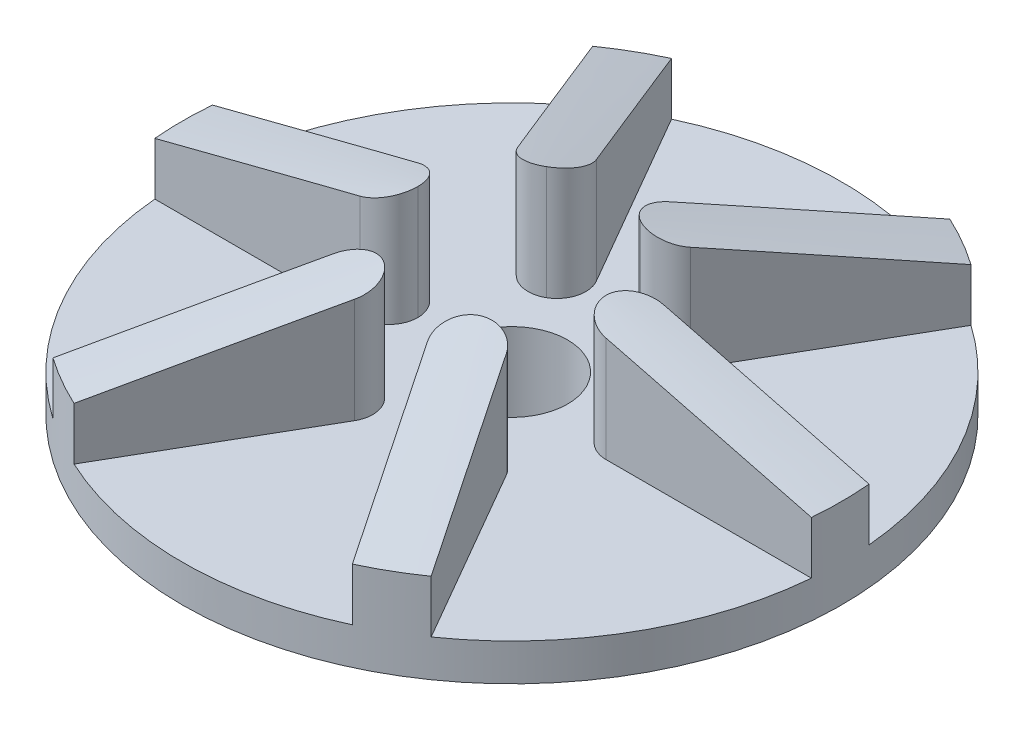
SolidWorks part; units mm, degrees
ref_plane "Front Plane" through (0, 0, 0) normal (0, 0, 1) x (1, 0, 0)
ref_plane "Top Plane" through (0, 0, 0) normal (0, 1, 0) x (1, 0, 0)
ref_plane "Right Plane" through (0, 0, 0) normal (1, 0, 0) x (0, 0, -1)
sketch "Sketch1" plane through (0, 0, 0) normal (0, 1, 0) x (1, 0, 0)
  circle A0 centre (0, 0) radius 17.78
  dimension "D1" = 35.56
extrude "base" add sketch "Sketch1" along normal blind 2
sketch "Sketch2" plane through (0, 0, 0) normal (0, -1, 0) x (1, 0, 0)
  circle A0 centre (0, 0) radius 8
  dimension "D1" = 16
extrude "boss" add sketch "Sketch2" along normal blind 5
sketch "Sketch3" plane through (0, 2, 0) normal (0, 1, 0) x (1, 0, 0)
  line L0 (5.08, 0) -> (17.78, 0) construction
  line L1 (4.8359, 1.5559) -> (17.7118, 1.5559)
  line L2 (4.8359, -1.5559) -> (17.7118, -1.5559)
  circle A0 centre (0, 0) radius 5.08 construction
  circle A1 centre (0, 0) radius 17.78 construction
  arc A2 (4.8359, -1.5559) -> (4.8359, 1.5559) centre (0, 0) ccw
  arc A3 (17.7118, -1.5559) -> (17.7118, 1.5559) centre (0, 0) ccw
  dimension "D1" = 10.16
  dimension "D2" = 1.5559
  dimension "D3" = 1.5559
extrude "blade" add sketch "Sketch3" along normal blind 6.1242
pattern_circular "blade pattern" count 6 over 360 about axis through (0, 0, 0) along (0, 1, 0) of "blade"
sketch "Sketch5" plane through (0, 0, 0) normal (0, 0, 1) x (1, 0, 0)
  line L0 (-17.78, 8.1242) -> (-17.78, 4.8372)
  line L2 (-17.78, 4.8372) -> (-5.08, 8.1242)
  line L3 (-5.08, 8.1242) -> (-17.78, 8.1242)
  line L4 (-10.2034, 2) -> (-17.7118, 2) construction
  line L5 (0, 0) -> (0, 16.9753) construction
  dimension "D1" = 2.8372
  dimension "D2" = 6.1242
  dimension "D3" = 17.78
  dimension "D4" = 5.08
revolve "angle trim" cut sketch "Sketch5" angle 360 about L5
sketch "Sketch6" plane through (0, -5, 0) normal (0, -1, 0) x (-1, 0, 0)
  circle A0 centre (0, 0) radius 3
  dimension "D1" = 6
extrude "bore_cut" cut sketch "Sketch6" against normal blind 20
sketch "Sketch7" plane through (0, -5, 0) normal (0, -1, 0) x (1, 0, 0)
  line L1 (-5, -1) -> (5, -1)
  line L2 (-5, -1) -> (-5, 1) construction
  line L3 (-5, 1) -> (5, 1)
  line L4 (5, -1) -> (5, 1) construction
  line L5 (-5, -1) -> (5, 1) construction
  line L6 (-5, 1) -> (5, -1) construction
  arc A0 (-5, 1) -> (-5, -1) centre (-5, 0) ccw
  arc A1 (5, -1) -> (5, 1) centre (5, 0) ccw
  point P0 (0, 0)
  dimension "D1" = 2
  dimension "D2" = 10
extrude "dowel cut" cut sketch "Sketch7" against normal blind 2
fillet "Fillet1" radius 1.5559 12 edges at (-4.8359, 5.0621, -1.5559) (-4.8359, 5.0621, 1.5559) (4.8359, 5.0621, 1.5559) (4.8359, 5.0621, -1.5559) (1.0705, 5.0621, -4.9659) (3.7654, 5.0621, -3.41) (-1.0705, 5.0621, -4.9659) (-3.7654, 5.0621, -3.41) (1.0705, 5.0621, 4.9659) (3.7654, 5.0621, 3.41) (-1.0705, 5.0621, 4.9659) (-3.7654, 5.0621, 3.41)
equation "\"z\" = 6"
equation "\"de\" = .4in"
equation "\"d2\" = 1.4in"
equation "\"theta\" = 15"
equation "\"b1\" = \"b2\" + (\"d2\"/2 - \"de\"/2)*sin(\"theta\")"
equation "\"b2\" = .1117in"
equation "\"s\" = ( 1/\"z\")*(3.14*\"de\" - (3.14*(\"de\"^2) / (4*(\"b1\"))))"
equation "\"bearing OD\" = 20mm"
equation "\"bearing outer race thickness\"= 1mm"
equation "\"bearing ID\"= 10mm"
equation "\"bearing depth\"= 6mm"
equation "\"bearing inner race thickness\"= 1mm"
equation "\"seal OD\" = 20mm"
equation "\"seal ID\"= 8mm"
equation "\"seal depth\"= 6mm"
equation "\"impeller base outer diameter\"= \"d2\""
equation "\"impeller base outer thickness\"= 2mm"
equation "\"impeller base center thickness\"= \"impeller base outer thickness\""
equation "\"impeller number of vanes\"= \"z\""
equation "\"impeller vane outer height\"= \"b2\""
equation "\"impeller vane inner height\"= \"b1\""
equation "\"impeller primary vane opening diamater\"= \"de\""
equation "\"impeller vane inner thickness\"= \"s\""
equation "\"impeller vane outer thickness\"= \"s\""
equation "\"impeller primary vane entrance angle\"= 0deg"
equation "\"impeller secondary vane entrance angle\"= 0deg"
equation "\"impeller secondary vane opening diameter\"= \"de\""
equation "\"impeller bolt surface height\" = 5mm"
equation "\"impeller bolt surface diameter\" = 8mm"
equation "\"impeller boss depth\" = 5mm"
equation "\"impeller dowel diameter\" = 2mm"
equation "\"motor to housing distance\"= 60mm"
equation "\"motor mount pattern diameter\"= 30mm"
equation "\"motor mount coupler shaft hole diameter\"= \"coupler shaft base diameter\"+ 4mm"
equation "\"motor mount to housing m8 screw hole diameter\"= 8.5mm"
equation "\"motor mount to housing m8 screw post radius\"= ( 3 * \"motor mount to housing m8 screw hole diameter\" ) / 2"
equation "\"motor mount to housing m8 pattern diameter\"= 100mm"
equation "\"motor mount to housing m4 screw hole diamater\"= 4mm"
equation "\"motor mount to housing m4 head diameter\"= 7.25mm"
equation "\"motor mount to housing m4 head depth\"= 4mm"
equation "\"motor mount plate thickness\"= 6mm + \"motor mount to housing m4 head depth\""
equation "\"housing bearing seat lip thickness\" = 2mm"
equation "\"housing base thickness\"= \"housing bearing seat lip thickness\" + \"seal depth\" + \"bearing depth\""
equation "\"housing top impeller vertical clearance\"= .5mm"
equation "\"housing top impeller horizontal clearance\"= .5mm"
equation "\"housing top impeller bottom clearance\"= 1mm"
equation "\"housing top impeller cavity height\"= \"housing top impeller bottom clearance\" + \"impeller base center thickness\" + \"impeller vane inner height\" + \"housing top impeller vertical clearance\""
equation "\"housing top impeller cavity diameter\"= 2 * \"housing top impeller horizontal clearance\" + \"impeller base outer diameter\""
equation "\"housing top impeller cavity tip height\"= \"housing top impeller bottom clearance\" + \"housing top impeller vertical clearance\" + \"impeller base outer thickness\" + \"impeller vane outer height\""
equation "\"housing top entrance OD\"= 20mm"
equation "\"housing top exit OD\"= \"d_exit\""
equation "\"housing top o-ring channel height\"= 1.5mm"
equation "\"housing top o ring channel width\"= 1.5mm"
equation "\"housing top o-ring circumference\" = 250mm"
equation "\"housing top o-ring radius\" = (\"housing top o-ring circumference\")/(2*3.14)"
equation "\"housing top threaded inlet depth\"= 8mm"
equation "\"housing top total thickness\"= \"housing top threaded inlet depth\" + \"housing top impeller cavity height\""
equation "\"housing top total width\"= 10mm"
equation "\"housing top exit threaded diameter\"= 8mm"
equation "\"housing top exit threaded depth\"= 8mm"
equation "\"motor shaft pride\"= 32mm"
equation "\"motor shaft flat section length from tip\"= 25.7mm"
equation "\"motor shaft bore end clearance\"= 2mm"
equation "\"coupler shaft to motor clearance\" = 2mm"
equation "\"motor mount shaft hole depth\"= \"motor shaft pride\""
equation "\"coupler shaft set screw drill hole diameter\"= 6mm"
equation "\"coupler shaft set screw 1 distance\"= \"motor mount shaft hole depth\" / 3"
equation "\"coupler shaft set screw 2 distance\"= \"motor mount shaft hole depth\" * 4 / 5"
equation "\"coupler shaft motor shaft hole diameter\"= 8mm"
equation "\"coupler shaft base diameter\"= 18mm"
equation "\"coupler shaft base length\"= \"motor mount shaft hole depth\" + 10mm"
equation "\"coupler shaft second section diameter\"= \"bearing ID\" + \"bearing inner race thickness\" * 2"
equation "\"coupler shaft second section length\"= \"motor to housing distance\" -  \"coupler shaft base length\" - 2mm"
equation "\"coupler shaft third section diamater\"= \"bearing ID\""
equation "\"coupler shaft third section length\"= \"bearing depth\""
equation "\"coupler shaft seal section diameter\" = \"seal ID\""
equation "\"coupler shaft seal section length\" = \"housing base thickness\"+\"housing top impeller bottom clearance\"-\"bearing depth\""
equation "\"coupler shaft impeller section diameter\" = 6mm"
equation "\"coupler shaft impeller section length\" = \"impeller boss depth\"+\"impeller base center thickness\" - 1mm"
equation "\"coupler shaft impeller screw hole diameter\" = \"motor mount to housing m4 screw hole diamater\""
equation "\"coupler shaft impeller screw hole depth\" = 10mm"
equation "\"impeller boss diameter\" = \"coupler shaft impeller section diameter\"+2*5mm"
equation "\"impeller dowel length\" = 2mm*2 + \"coupler shaft impeller section diameter\""
equation "\"D1@Sketch1\"=\"d2\""
equation "\"D1@base\" = \"impeller base outer thickness\""
equation "\"D1@Sketch2\"=\"impeller boss diameter\""
equation "\"D1@boss\" = \"impeller boss depth\""
equation "\"D1@Sketch3\"=\"de\""
equation "\"D2@Sketch3\"=\"s\"/2"
equation "\"D3@Sketch3\"=\"s\"/2"
equation "\"D1@blade\" = \"b1\""
equation "\"D1@blade pattern\"=\"z\""
equation "\"D1@Sketch5\"=\"b2\""
equation "\"D2@Sketch5\"=\"b1\""
equation "\"D3@Sketch5\"=\"d2\"/2"
equation "\"D4@Sketch5\"=\"de\"/2"
equation "\"s_opening\" = (3.14*\"de\" - \"z\"*\"s\")/\"z\""
equation "\"D1@bore_cut\" = 20mm"
equation "\"D1@Sketch6\"=\"coupler shaft impeller section diameter\""
equation "\"D1@Sketch7\"=\"impeller dowel diameter\""
equation "\"D2@Sketch7\"=\"impeller dowel length\""
equation "\"D1@dowel cut\" = \"impeller dowel diameter\""
equation "\"d_exit\" = .25in"
equation "\"area_eye\"=3.14*(\"de\"^2)/4"
equation "\"single_channel_area\"=\"s_opening\"*\"b1\""
equation "\"D1@Fillet1\"=\"s\"/2"
